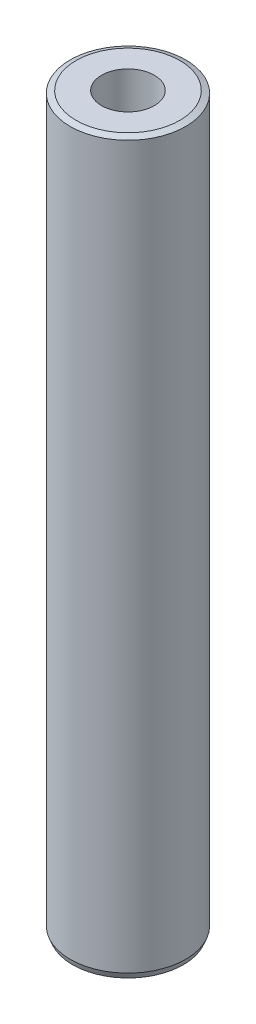
SolidWorks part; units mm, degrees
ref_plane "Front Plane" through (0, 0, 0) normal (0, 0, 1) x (1, 0, 0)
ref_plane "Top Plane" through (0, 0, 0) normal (0, 1, 0) x (1, 0, 0)
ref_plane "Right Plane" through (0, 0, 0) normal (1, 0, 0) x (0, 0, -1)
sketch "Sketch1" plane through (0, 0, 0) normal (0, 1, 0) x (1, 0, 0)
  circle A0 centre (0, 0) radius 47.5
  dimension "SHAFT_OD" = 95
extrude "Boss-Extrude1" add sketch "Sketch1" along normal blind 600
sketch "Sketch2" plane through (0, 0, 0) normal (0, 1, 0) x (1, 0, 0)
  circle A0 centre (0, 0) radius 21.7029
  dimension "BORE_D" = 43.4058
extrude "Cut-Extrude1" cut sketch "Sketch2" along normal through all
chamfer "Chamfer1" distance 1.9287 angle 68.268 2 edges at (0, 600, 47.5) (0, 0, 47.5) first distance on face at (0, 600, 47.5) first distance on face at (0, 0, 21.7029)
